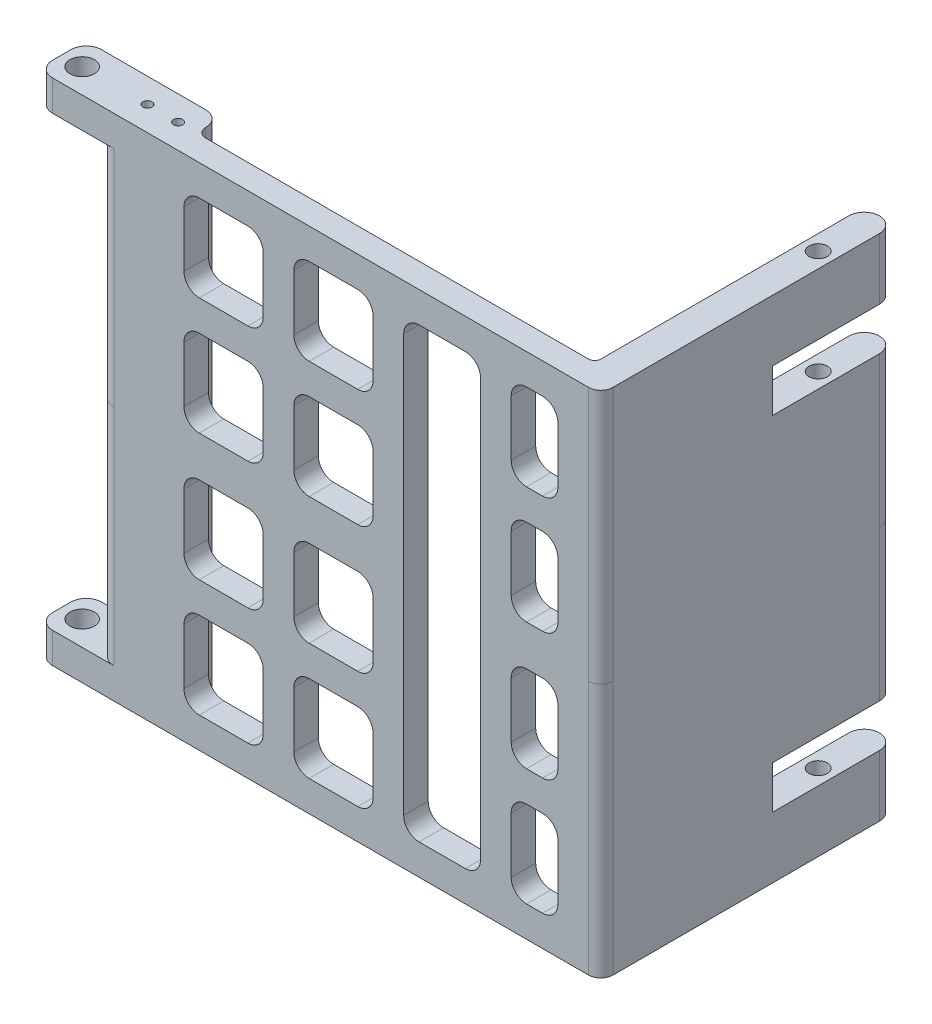
SolidWorks part; units mm, degrees
material "ABS"
ref_plane "Plano frontal" through (0, 0, 0) normal (0, 0, 1) x (1, 0, 0)
ref_plane "Plano superior" through (0, 0, 0) normal (0, 1, 0) x (1, 0, 0)
ref_plane "Plano direito" through (0, 0, 0) normal (1, 0, 0) x (0, 0, -1)
sketch "Esboço2" plane through (0, 0, 0) normal (0, 0, 1) x (1, 0, 0)
  line L1 (-67.2812, 6.4424) -> (14.7188, 6.4424)
  line L2 (-67.2812, 6.4424) -> (-67.2812, -35.1076)
  line L3 (-67.2812, -35.1076) -> (14.7188, -35.1076)
  line L4 (14.7188, 6.4424) -> (14.7188, -35.1076)
extrude "Ressalto-extrusão1" add sketch "Esboço2" along normal blind 8
sketch "Esboço3" plane through (0, -35.1076, 0) normal (0, -1, 0) x (-1, 0, 0)
  line L0 (50.5731, -0.27) -> (50.5731, -7.73) construction
  line L1 (50.5731, -7.73) -> (50.1981, -7.73) construction
  line L3 (55.6594, -4) -> (67.2812, -4) construction
  line L4 (67.2812, -8) -> (67.2812, 0) construction
  line L5 (67.2812, 0) -> (-14.7188, 0) construction
  line L7 (50.5731, -7.73) -> (50.9481, -7.73) construction
  circle A5 centre (58.2812, -4) radius 0.75
  circle A7 centre (63.2812, -4) radius 0.75
  dimension "D1" = 4
  dimension "D2" = 5
  dimension "D7" = 7.46
  dimension "D8" = 0.27
  dimension "D9" = 0
extrude "Corte-extrusão1" cut sketch "Esboço3" against normal through all
sketch "Esboço7" plane through (14.7188, 0, 0) normal (1, 0, 0) x (0, 0, -1)
  line L1 (0, 6.4424) -> (40, 6.4424)
  line L2 (0, 6.4424) -> (0, -35.1076)
  line L3 (0, -35.1076) -> (40, -35.1076)
  line L4 (40, 6.4424) -> (40, -35.1076)
extrude "Ressalto-extrusão2" add sketch "Esboço7" against normal blind 5
fillet "Filete1" radius 2 1 edges at (14.7188, -14.3326, 8)
sketch "Esboço11" plane through (0, 0, 8) normal (0, 0, 1) x (1, 0, 0)
  line L0 (-67.2812, 3.1324) -> (12.7188, 3.1324) construction
  line L1 (-67.2812, -35.1076) -> (12.7188, -35.1076) construction
  line L2 (12.7188, -35.1076) -> (12.7188, 6.4424) construction
  line L3 (12.7188, 6.4424) -> (-67.2812, 6.4424) construction
  line L4 (-62.2812, -35.1076) -> (-62.2812, 6.4424) construction
  line L5 (-67.2812, -35.1076) -> (12.7188, -35.1076) construction
  line L6 (7.7188, -35.1076) -> (7.7188, 6.4424) construction
  line L7 (-67.2812, -30.1076) -> (12.7188, -30.1076) construction
  line L13 (-67.2812, 6.4424) -> (-67.2812, -35.1076) construction
  line L17 (-50.8312, -30.1076) -> (-42.8912, -30.1076)
  line L18 (-53.3312, -27.6076) -> (-53.3312, -18.4876)
  line L19 (-50.8312, -15.9876) -> (-42.8912, -15.9876)
  line L20 (-40.3912, -27.6076) -> (-40.3912, -18.4876)
  line L21 (-50.8312, 3.1324) -> (-42.8912, 3.1324)
  line L22 (-53.3312, 0.6324) -> (-53.3312, -8.4876)
  line L23 (-50.8312, -10.9876) -> (-42.8912, -10.9876)
  line L24 (-40.3912, 0.6324) -> (-40.3912, -8.4876)
  line L25 (5.2188, 3.1324) -> (2.5988, 3.1324)
  line L26 (7.7188, 0.6324) -> (7.7188, -8.4876)
  line L27 (5.2188, -10.9876) -> (2.5988, -10.9876)
  line L28 (0.0988, 0.6324) -> (0.0988, -8.4876)
  line L29 (5.2188, -30.1076) -> (2.5988, -30.1076)
  line L30 (7.7188, -27.6076) -> (7.7188, -18.4876)
  line L31 (5.2188, -15.9876) -> (2.5988, -15.9876)
  line L32 (0.0988, -27.6076) -> (0.0988, -18.4876)
  line L33 (-4.9012, 6.4424) -> (-17.4512, 6.4424)
  line L34 (-4.9012, 6.4424) -> (-4.9012, -27.6076)
  line L35 (-7.4012, -30.1076) -> (-14.9512, -30.1076)
  line L36 (-17.4512, 6.4424) -> (-17.4512, -27.6076)
  line L37 (-32.8912, -30.1076) -> (-24.9512, -30.1076)
  line L38 (-35.3912, -27.6076) -> (-35.3912, -18.4876)
  line L39 (-32.8912, -15.9876) -> (-24.9512, -15.9876)
  line L40 (-22.4512, -27.6076) -> (-22.4512, -18.4876)
  line L41 (-32.8912, 3.1324) -> (-24.9512, 3.1324)
  line L42 (-35.3912, 0.6324) -> (-35.3912, -8.4876)
  line L43 (-32.8912, -10.9876) -> (-24.9512, -10.9876)
  line L44 (-22.4512, 0.6324) -> (-22.4512, -8.4876)
  arc A0 (-14.9512, -30.1076) -> (-17.4512, -27.6076) centre (-14.9512, -27.6076) cw
  arc A1 (-7.4012, -30.1076) -> (-4.9012, -27.6076) centre (-7.4012, -27.6076) ccw
  arc A2 (7.7188, -8.4876) -> (5.2188, -10.9876) centre (5.2188, -8.4876) cw
  arc A3 (5.2188, 3.1324) -> (7.7188, 0.6324) centre (5.2188, 0.6324) cw
  arc A4 (2.5988, 3.1324) -> (0.0988, 0.6324) centre (2.5988, 0.6324) ccw
  arc A5 (2.5988, -10.9876) -> (0.0988, -8.4876) centre (2.5988, -8.4876) cw
  arc A6 (7.7188, -18.4876) -> (5.2188, -15.9876) centre (5.2188, -18.4876) ccw
  arc A7 (5.2188, -30.1076) -> (7.7188, -27.6076) centre (5.2188, -27.6076) ccw
  arc A8 (2.5988, -30.1076) -> (0.0988, -27.6076) centre (2.5988, -27.6076) cw
  arc A9 (2.5988, -15.9876) -> (0.0988, -18.4876) centre (2.5988, -18.4876) ccw
  arc A10 (-24.9512, -30.1076) -> (-22.4512, -27.6076) centre (-24.9512, -27.6076) ccw
  arc A11 (-24.9512, -15.9876) -> (-22.4512, -18.4876) centre (-24.9512, -18.4876) cw
  arc A12 (-32.8912, -30.1076) -> (-35.3912, -27.6076) centre (-32.8912, -27.6076) cw
  arc A13 (-35.3912, -18.4876) -> (-32.8912, -15.9876) centre (-32.8912, -18.4876) cw
  arc A14 (-24.9512, -10.9876) -> (-22.4512, -8.4876) centre (-24.9512, -8.4876) ccw
  arc A15 (-24.9512, 3.1324) -> (-22.4512, 0.6324) centre (-24.9512, 0.6324) cw
  arc A16 (-32.8912, 3.1324) -> (-35.3912, 0.6324) centre (-32.8912, 0.6324) ccw
  arc A17 (-35.3912, -8.4876) -> (-32.8912, -10.9876) centre (-32.8912, -8.4876) ccw
  arc A18 (-42.8912, 3.1324) -> (-40.3912, 0.6324) centre (-42.8912, 0.6324) cw
  arc A19 (-50.8312, 3.1324) -> (-53.3312, 0.6324) centre (-50.8312, 0.6324) ccw
  arc A20 (-42.8912, -10.9876) -> (-40.3912, -8.4876) centre (-42.8912, -8.4876) ccw
  arc A21 (-53.3312, -18.4876) -> (-50.8312, -15.9876) centre (-50.8312, -18.4876) cw
  arc A22 (-42.8912, -15.9876) -> (-40.3912, -18.4876) centre (-42.8912, -18.4876) cw
  arc A23 (-42.8912, -30.1076) -> (-40.3912, -27.6076) centre (-42.8912, -27.6076) ccw
  arc A24 (-50.8312, -30.1076) -> (-53.3312, -27.6076) centre (-50.8312, -27.6076) cw
  arc A25 (-53.3312, -8.4876) -> (-50.8312, -10.9876) centre (-50.8312, -8.4876) ccw
  point P35 (0.0988, 3.1324)
  point P41 (-17.4512, -30.1076)
  point P54 (7.7188, 3.1324)
  point P69 (0.0988, -23.0476)
  point P79 (-35.3912, -30.1076)
  point P88 (-35.3912, 3.1324)
  point P95 (-53.3312, 3.1324)
  point P100 (-53.3312, -15.9876)
  point P103 (-40.3912, -15.9876)
  point P108 (-53.3312, -30.1076)
  dimension "D8" = 5
  dimension "D7" = 5
  dimension "D3" = 5
  dimension "D4" = 5
  dimension "D6" = 5
  dimension "D15" = 44.83
  dimension "D16" = 5
  dimension "D17" = 5
  dimension "D18" = 5
  dimension "D19" = 5
  dimension "D20" = 5
  dimension "D21" = 5
extrude "Corte-extrusão3" cut sketch "Esboço11" against normal blind 8 and the other way through all
sketch "Esboço12" plane through (14.7188, 0, 0) normal (1, 0, 0) x (0, 0, -1)
  line L0 (40, -35.1076) -> (40, 6.4424) construction
  line L1 (40, -25.1076) -> (20, -25.1076)
  line L2 (40, -25.1076) -> (40, -18.1076)
  line L3 (40, -18.1076) -> (20, -18.1076)
  line L4 (20, -25.1076) -> (20, -18.1076)
  line L5 (-6, -35.1076) -> (40, -35.1076) construction
  dimension "D1" = 10
extrude "Corte-extrusão4" cut sketch "Esboço12" against normal blind 10
sketch "Esboço17" plane through (0, 0, 0) normal (0, 0, -1) x (-1, 0, 0)
  line L1 (67.2812, -35.1076) -> (77.2812, -35.1076)
  line L2 (67.2812, -35.1076) -> (67.2812, -30.1076)
  line L3 (67.2812, -30.1076) -> (77.2812, -30.1076)
  line L4 (77.2812, -35.1076) -> (77.2812, -30.1076)
sketch "Esboço19" plane through (0, -35.1076, 0) normal (0, -1, 0) x (1, 0, 0)
  line L0 (9.7188, 0) -> (9.7188, -40) construction
  line L1 (9.7188, -40) -> (14.7188, -40) construction
  circle A0 centre (12.2188, -30) radius 1.5
  dimension "D1" = 2.5
  dimension "D2" = 10
extrude "Corte-extrusão7" cut sketch "Esboço19" against normal through all
extrude "Ressalto-extrusão4" add sketch "Esboço17" against normal blind 8
sketch "Esboço20" plane through (0, -35.1076, 0) normal (0, -1, 0) x (1, 0, 0)
  line L0 (-77.2812, 8) -> (12.7188, 8) construction
  circle A0 centre (-73.9512, 4) radius 2
  circle A1 centre (-63.2812, 4) radius 0.75 construction
  dimension "D1" = 4
  dimension "D2" = 10.67
extrude "Corte-extrusão9" cut sketch "Esboço20" against normal blind 8 contours A0
fillet "Filete2" radius 2.5 1 edges at (-67.2812, -11.8326, 8)
fillet "Filete3" radius 2.5 1 edges at (-67.2812, -11.8326, 0)
fillet "Filete4" radius 2.5 1 edges at (-77.2812, -32.6076, 8)
fillet "Filete5" radius 2.5 1 edges at (-77.2812, -32.6076, 0)
sketch "Esboço25" plane through (0, -35.1076, 0) normal (0, -1, 0) x (1, 0, 0)
  line L0 (-55.2812, 0) -> (9.7188, 0)
  line L1 (-55.2812, 0) -> (-55.2812, 4)
  line L2 (9.7188, 0) -> (9.7188, 4)
  line L3 (-55.2812, 4) -> (9.7188, 4)
  circle A1 centre (-58.2812, 4) radius 0.75 construction
  dimension "D1" = 4
  dimension "D2" = 3
extrude "Corte-extrusão10" cut sketch "Esboço25" against normal through all
fillet "Filete8" radius 1 1 edges at (9.7188, -14.3326, 4)
fillet "Filete9" radius 2.5 1 edges at (14.7188, -30.1076, -40)
fillet "Filete10" radius 2.5 3 edges at (9.7188, -30.1076, -40) (9.7188, -5.8326, -40) (14.7188, -5.8326, -40)
fillet "Filete11" radius 2.5 1 edges at (-55.2812, -14.3326, 0)
fillet "Filete12" radius 1.5 1 edges at (-55.2812, -14.3326, 4)
ref_plane "Plano1" through (0, 6.4424, 0) normal (0, 1, 0) x (1, 0, 0)
mirror "Espelhar1" about plane through (0, 6.4424, 0) normal (0, 1, 0) of "Ressalto-extrusão1", "Corte-extrusão1", "Ressalto-extrusão2", "Filete1", "Corte-extrusão3", "Corte-extrusão4", "Corte-extrusão7", "Ressalto-extrusão4", "Corte-extrusão9", "Filete2", "Filete3", "Filete4", "Filete5", "Corte-extrusão10", "Filete8", "Filete9", "Filete10", "Filete11", "Filete12"
